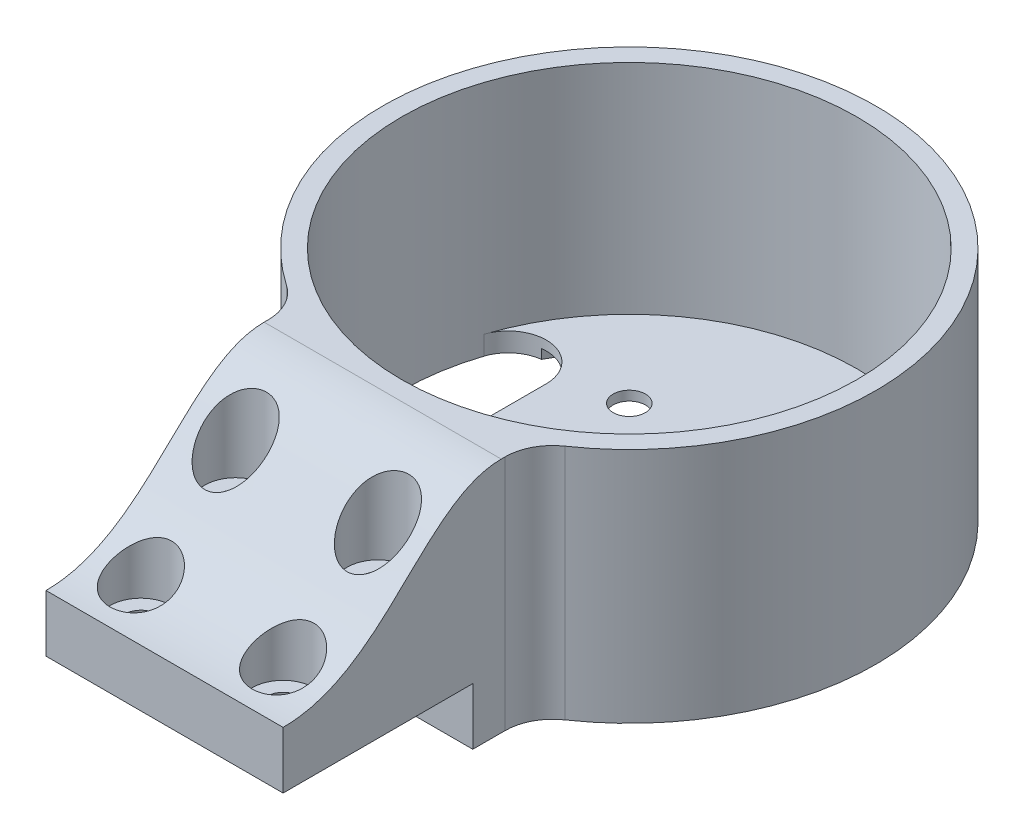
SolidWorks part; units mm, degrees
material "Сплав 2024"
ref_plane "Спереди" through (0, 0, 0) normal (0, 0, 1) x (1, 0, 0)
ref_plane "Сверху" through (0, 0, 0) normal (0, 1, 0) x (1, 0, 0)
ref_plane "Справа" through (0, 0, 0) normal (1, 0, 0) x (0, 0, -1)
sketch "Эскиз1" plane through (0, 0, 0) normal (0, 1, 0) x (1, 0, 0)
  circle A0 centre (0, 0) radius 26
  dimension "D1" = 52
extrude "Бобышка-Вытянуть1" add sketch "Эскиз1" along normal blind 2
sketch "Эскиз2" plane through (0, 2, 0) normal (0, 1, 0) x (1, 0, 0)
  circle A0 centre (0, 0) radius 26 construction
  circle A1 centre (0, 0) radius 26
  circle A2 centre (0, 0) radius 24
  dimension "D1" = 48
extrude "Бобышка-Вытянуть2" add sketch "Эскиз2" along normal blind 23
sketch "Эскиз3" plane through (0, 25, 0) normal (0, 1, 0) x (1, 0, 0)
  line L0 (0, -26) -> (0, -49) construction
  circle A0 centre (0, 0) radius 26 construction
  dimension "D1" = 23
ref_plane "Плоскость1" through (0, 0, 49) normal (0, 0, 1) x (1, 0, 0)
sketch "Эскиз4" plane through (0, 0, 49) normal (0, 0, 1) x (1, 0, 0)
  line L0 (-26, 0) -> (26, 0) construction
  line L1 (-12.5, 12) -> (12.5, 12)
  line L2 (-12.5, 12) -> (-12.5, 0)
  line L3 (-12.5, 0) -> (12.5, 0)
  line L4 (12.5, 12) -> (12.5, 0)
  point P4 (0, 0)
  dimension "D1" = 12
  dimension "D2" = 25
extrude "Бобышка-Вытянуть3" add sketch "Эскиз4" against normal up to surface (26.202 mm away) up to face at (0, 0, 26)
sketch "Эскиз5" plane through (0, 0, 0) normal (0, -1, 0) x (1, 0, 0)
  line L0 (12.5, 22.798) -> (12.5, 49) construction
  line L1 (-12.5, 49) -> (12.5, 49)
  line L2 (-12.5, 49) -> (-12.5, 29)
  line L3 (-12.5, 29) -> (12.5, 29)
  line L4 (12.5, 49) -> (12.5, 29)
  dimension "D1" = 20
extrude "Вырез-Вытянуть1" cut sketch "Эскиз5" against normal blind 6
sketch "Эскиз6" plane through (12.5, 0, 0) normal (1, 0, 0) x (0, 0, -1)
  line L0 (-20.3576, 25) -> (-31.6544, 25) construction
  line L1 (-26, 25) -> (-22.798, 25)
  line L2 (24, 25) -> (-24, 25) construction
  line L3 (-22.798, 25) -> (-22.798, 12)
  line L4 (-22.798, 12) -> (-49, 12)
  line L5 (-42.591, 12) -> (-55.4136, 12) construction
  spline S0 degree 3 poles (-49, 12) (-38.3413, 12) (-34.1299, 25) (-26, 25) knots 0 0 0 0 1 1 1 1
extrude "Бобышка-Вытянуть5" add sketch "Эскиз6" against normal up to surface (25 mm away) up to face at (-12.5, 6, 33.5993)
sketch "Эскиз7" plane through (0, 25, 0) normal (0, 1, 0) x (1, 0, 0)
  circle A0 centre (0, 0) radius 24
  circle A1 centre (0, 0) radius 24 construction
extrude "Вырез-Вытянуть2" cut sketch "Эскиз7" against normal up to surface (23 mm away) up to face at (0, 2, 24)
sketch "Эскиз8" plane through (0, 0, 0) normal (0, -1, 0) x (1, 0, 0)
  circle A0 centre (0, 0) radius 24 construction
  circle A1 centre (0, 0) radius 24
  arc A2 (-12.5, 22.798) -> (12.5, 22.798) centre (0, 0) ccw construction
  arc A3 (-12.5, 22.798) -> (12.5, 22.798) centre (0, 0) ccw
  arc A4 (-12.5, 22.798) -> (12.5, 22.798) centre (0, 0) cw
extrude "Бобышка-Вытянуть6" add sketch "Эскиз8" along normal blind 5
fillet "Скругление1" radius 5 2 edges
sketch "Эскиз9" plane through (0, -5, 0) normal (0, -1, 0) x (1, 0, 0)
  circle A0 centre (0, 0) radius 24 construction
  circle A1 centre (0, 0) radius 26
  circle A2 centre (0, 0) radius 26
  circle A3 centre (0, 0) radius 24
  dimension "D1" = 0
extrude "Вырез-Вытянуть3" cut sketch "Эскиз9" against normal up to surface (5 mm away)
sketch "Эскиз10" plane through (0, 0, 0) normal (0, -1, 0) x (1, 0, 0)
  circle A0 centre (0, 0) radius 22
  dimension "D1" = 44
extrude "Вырез-Вытянуть4" cut sketch "Эскиз10" against normal blind 1
sketch "Эскиз11" plane through (0, 1, 0) normal (0, -1, 0) x (1, 0, 0)
  circle A0 centre (0, 0) radius 7
  dimension "D1" = 14
extrude "Вырез-Вытянуть5" cut sketch "Эскиз11" against normal up to next
sketch "Эскиз12" plane through (0, 1, 0) normal (0, -1, 0) x (1, 0, 0)
  line L1 (8.8388, -8.8388) -> (-8.8388, -8.8388) construction
  line L2 (8.8388, -8.8388) -> (8.8388, 8.8388) construction
  line L3 (8.8388, 8.8388) -> (-8.8388, 8.8388) construction
  line L4 (-8.8388, -8.8388) -> (-8.8388, 8.8388) construction
  line L5 (8.8388, -8.8388) -> (-8.8388, 8.8388) construction
  line L6 (8.8388, 8.8388) -> (-8.8388, -8.8388) construction
  point P0 (0, 0)
  dimension "D1" = 25
hole_wizard "Отверстие с зазором M31" positions "Эскиз14" profile "Эскиз13" hole size "M3" standard "Ansi Metric" end condition up to next
sketch "Эскиз14" plane through (0, 1, 0) normal (0, -1, 0) x (-1, 0, 0)
  point P0 (8.8388, -8.8388)
  point P3 (8.8388, 8.8388)
  point P6 (-8.8388, 8.8388)
  point P9 (-8.8388, -8.8388)
sketch "Эскиз13" plane through (-8.8388, 1, 8.8388) normal (1, 0, 0) x (0, 0, -1)
  line L0 (0, 0) -> (0, 1)
  line L1 (0, 1) -> (1.7, 1)
  line L2 (1.7, 1) -> (1.7, 0)
  line L5 (1.7, 0) -> (0, 0)
  line L11 (0, -6.35) -> (0, 107.95) construction
  dimension "Диаметр сквозного отверстия" = 3.4
  dimension "Глубина сквозного отверстия" = 1
sketch "Эскиз15" plane through (0, 1, 0) normal (0, -1, 0) x (1, 0, 0)
  line L0 (-15, 18.735) -> (-15, -18.735)
  circle A1 centre (0, 0) radius 24 construction
  arc A2 (-15, 18.735) -> (-15, -18.735) centre (0, 0) ccw
  dimension "D1" = 15
extrude "Вырез-Вытянуть6" cut sketch "Эскиз15" against normal up to next and the other way up to next
fillet "Скругление2" radius 4 1 edges at (-15, 1, 18.735)
fillet "Скругление3" radius 4 1 edges at (-15, 1, -18.735)
sketch "Эскиз16" plane through (0, 25, 0) normal (0, 1, 0) x (1, 0, 0)
  line L0 (0, -49) -> (0, -20.7407) construction
  line L1 (12.5, -49) -> (-12.5, -49) construction
  line L2 (12.5, -49) -> (12.5, -26) construction
  line L3 (-7.5, -34) -> (7.5, -34) construction
  line L4 (-7.5, -34) -> (-7.5, -44) construction
  line L5 (-7.5, -44) -> (7.5, -44) construction
  line L6 (7.5, -34) -> (7.5, -44) construction
  line L7 (-7.5, -34) -> (7.5, -44) construction
  line L8 (-7.5, -44) -> (7.5, -34) construction
  point P5 (0, -39)
  dimension "D1" = 5
  dimension "D2" = 5
  dimension "D3" = 10
hole_wizard "Цековка для винта с внутренним шестигранником M31" positions "Эскиз18" profile "Эскиз17" counterbore size "M3" standard "Ansi Metric" end condition through all
sketch "Эскиз18" plane through (0, 25, 0) normal (0, 1, 0) x (1, 0, 0)
  point P0 (-7.5, -34)
  point P3 (7.5, -34)
sketch "Эскиз17" plane through (-7.5, 25, 34) normal (1, 0, 0) x (0, 0, 1)
  line L0 (0, 0) -> (0, 25)
  line L1 (0, 25) -> (1.7, 25)
  line L3 (1.7, 25) -> (1.7, 10)
  line L4 (1.7, 10) -> (3.25, 10)
  line L5 (3.25, 10) -> (3.25, 0)
  line L7 (3.25, 0) -> (0, 0)
  line L11 (0, -6.35) -> (0, 107.95) construction
  dimension "Диаметр сквозного отверстия" = 3.4
  dimension "Глубина сквозного отверстия" = 25
  dimension "Диаметр цековки" = 6.5
  dimension "Глубина цековки" = 10
hole_wizard "Цековка для винта с внутренним шестигранником M32" positions "Эскиз20" profile "Эскиз19" counterbore size "M3" standard "Ansi Metric" end condition through all
sketch "Эскиз20" plane through (0, 25, 0) normal (0, 1, 0) x (1, 0, 0)
  point P0 (-7.5, -44)
  point P3 (7.5, -44)
sketch "Эскиз19" plane through (-7.5, 25, 44) normal (1, 0, 0) x (0, 0, 1)
  line L0 (0, 0) -> (0, 25)
  line L1 (0, 25) -> (1.7, 25)
  line L3 (1.7, 25) -> (1.7, 16)
  line L4 (1.7, 16) -> (3.25, 16)
  line L5 (3.25, 16) -> (3.25, 0)
  line L7 (3.25, 0) -> (0, 0)
  line L11 (0, -6.35) -> (0, 107.95) construction
  dimension "Диаметр сквозного отверстия" = 3.4
  dimension "Глубина сквозного отверстия" = 25
  dimension "Диаметр цековки" = 6.5
  dimension "Глубина цековки" = 16
